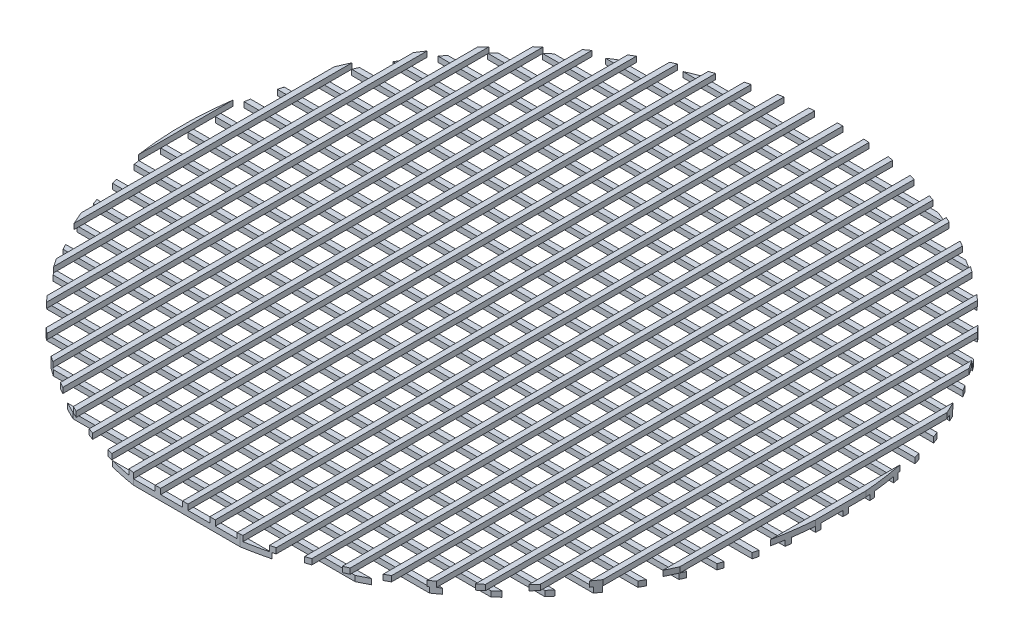
SolidWorks part; units mm, degrees
material "1023 Carbon Steel Sheet (SS)"
ref_plane "Front Plane" through (0, 0, 0) normal (0, 0, 1) x (1, 0, 0)
ref_plane "Top Plane" through (0, 0, 0) normal (0, 1, 0) x (1, 0, 0)
ref_plane "Right Plane" through (0, 0, 0) normal (1, 0, 0) x (0, 0, -1)
sketch "Sketch1" plane through (0, 0, 0) normal (0, 1, 0) x (1, 0, 0)
  line L0 (-34.035, 32.5183) -> (-33.935, 32.5183)
  line L1 (-34.535, 32.5183) -> (-34.435, 32.5183)
  line L2 (-34.535, 32.5183) -> (-34.535, 20.5183)
  line L3 (-34.535, 20.5183) -> (-34.435, 20.5183)
  line L4 (-34.435, 32.5183) -> (-34.435, 20.5183)
  line L5 (-34.035, 32.5183) -> (-34.035, 20.5183)
  line L6 (-34.035, 20.5183) -> (-33.935, 20.5183)
  line L7 (-33.935, 32.5183) -> (-33.935, 20.5183)
  line L8 (-33.535, 32.5183) -> (-33.435, 32.5183)
  line L9 (-33.535, 32.5183) -> (-33.535, 20.5183)
  line L10 (-33.535, 20.5183) -> (-33.435, 20.5183)
  line L11 (-33.435, 32.5183) -> (-33.435, 20.5183)
  line L12 (-33.035, 32.5183) -> (-32.935, 32.5183)
  line L13 (-33.035, 32.5183) -> (-33.035, 20.5183)
  line L14 (-33.035, 20.5183) -> (-32.935, 20.5183)
  line L15 (-32.935, 32.5183) -> (-32.935, 20.5183)
  line L16 (-32.535, 32.5183) -> (-32.435, 32.5183)
  line L17 (-32.535, 32.5183) -> (-32.535, 20.5183)
  line L18 (-32.535, 20.5183) -> (-32.435, 20.5183)
  line L19 (-32.435, 32.5183) -> (-32.435, 20.5183)
  line L20 (-32.035, 32.5183) -> (-31.935, 32.5183)
  line L21 (-32.035, 32.5183) -> (-32.035, 20.5183)
  line L22 (-32.035, 20.5183) -> (-31.935, 20.5183)
  line L23 (-31.935, 32.5183) -> (-31.935, 20.5183)
  line L24 (-31.535, 32.5183) -> (-31.435, 32.5183)
  line L25 (-31.535, 32.5183) -> (-31.535, 20.5183)
  line L26 (-31.535, 20.5183) -> (-31.435, 20.5183)
  line L27 (-31.435, 32.5183) -> (-31.435, 20.5183)
  line L28 (-31.035, 32.5183) -> (-30.935, 32.5183)
  line L29 (-31.035, 32.5183) -> (-31.035, 20.5183)
  line L30 (-31.035, 20.5183) -> (-30.935, 20.5183)
  line L31 (-30.935, 32.5183) -> (-30.935, 20.5183)
  line L32 (-30.535, 32.5183) -> (-30.435, 32.5183)
  line L33 (-30.535, 32.5183) -> (-30.535, 20.5183)
  line L34 (-30.535, 20.5183) -> (-30.435, 20.5183)
  line L35 (-30.435, 32.5183) -> (-30.435, 20.5183)
  line L36 (-30.035, 32.5183) -> (-29.935, 32.5183)
  line L37 (-30.035, 32.5183) -> (-30.035, 20.5183)
  line L38 (-30.035, 20.5183) -> (-29.935, 20.5183)
  line L39 (-29.935, 32.5183) -> (-29.935, 20.5183)
  line L40 (-29.535, 32.5183) -> (-29.435, 32.5183)
  line L41 (-29.535, 32.5183) -> (-29.535, 20.5183)
  line L42 (-29.535, 20.5183) -> (-29.435, 20.5183)
  line L43 (-29.435, 32.5183) -> (-29.435, 20.5183)
  line L44 (-29.035, 32.5183) -> (-28.935, 32.5183)
  line L45 (-29.035, 32.5183) -> (-29.035, 20.5183)
  line L46 (-29.035, 20.5183) -> (-28.935, 20.5183)
  line L47 (-28.935, 32.5183) -> (-28.935, 20.5183)
  line L48 (-28.535, 32.5183) -> (-28.435, 32.5183)
  line L49 (-28.535, 32.5183) -> (-28.535, 20.5183)
  line L50 (-28.535, 20.5183) -> (-28.435, 20.5183)
  line L51 (-28.435, 32.5183) -> (-28.435, 20.5183)
  line L52 (-35.035, 32.5183) -> (-34.935, 32.5183)
  line L53 (-35.035, 32.5183) -> (-35.035, 20.5183)
  line L54 (-35.035, 20.5183) -> (-34.935, 20.5183)
  line L55 (-34.935, 32.5183) -> (-34.935, 20.5183)
  line L56 (-35.535, 32.5183) -> (-35.435, 32.5183)
  line L57 (-35.535, 32.5183) -> (-35.535, 20.5183)
  line L58 (-35.535, 20.5183) -> (-35.435, 20.5183)
  line L59 (-35.435, 32.5183) -> (-35.435, 20.5183)
  line L60 (-36.035, 32.5183) -> (-35.935, 32.5183)
  line L61 (-36.035, 32.5183) -> (-36.035, 20.5183)
  line L62 (-36.035, 20.5183) -> (-35.935, 20.5183)
  line L63 (-35.935, 32.5183) -> (-35.935, 20.5183)
  line L64 (-36.535, 32.5183) -> (-36.435, 32.5183)
  line L65 (-36.535, 32.5183) -> (-36.535, 20.5183)
  line L66 (-36.535, 20.5183) -> (-36.435, 20.5183)
  line L67 (-36.435, 32.5183) -> (-36.435, 20.5183)
  line L68 (-37.035, 32.5183) -> (-36.935, 32.5183)
  line L69 (-37.035, 32.5183) -> (-37.035, 20.5183)
  line L70 (-37.035, 20.5183) -> (-36.935, 20.5183)
  line L71 (-36.935, 32.5183) -> (-36.935, 20.5183)
  line L72 (-37.535, 32.5183) -> (-37.435, 32.5183)
  line L73 (-37.535, 32.5183) -> (-37.535, 20.5183)
  line L74 (-37.535, 20.5183) -> (-37.435, 20.5183)
  line L75 (-37.435, 32.5183) -> (-37.435, 20.5183)
  line L76 (-38.035, 32.5183) -> (-37.935, 32.5183)
  line L77 (-38.035, 32.5183) -> (-38.035, 20.5183)
  line L78 (-38.035, 20.5183) -> (-37.935, 20.5183)
  line L79 (-37.935, 32.5183) -> (-37.935, 20.5183)
  line L80 (-38.535, 32.5183) -> (-38.435, 32.5183)
  line L81 (-38.535, 32.5183) -> (-38.535, 20.5183)
  line L82 (-38.535, 20.5183) -> (-38.435, 20.5183)
  line L83 (-38.435, 32.5183) -> (-38.435, 20.5183)
  line L84 (-39.035, 32.5183) -> (-38.935, 32.5183)
  line L85 (-39.035, 32.5183) -> (-39.035, 20.5183)
  line L86 (-39.035, 20.5183) -> (-38.935, 20.5183)
  line L87 (-38.935, 32.5183) -> (-38.935, 20.5183)
  line L88 (-39.535, 32.5183) -> (-39.435, 32.5183)
  line L89 (-39.535, 32.5183) -> (-39.535, 20.5183)
  line L90 (-39.535, 20.5183) -> (-39.435, 20.5183)
  line L91 (-39.435, 32.5183) -> (-39.435, 20.5183)
  line L92 (-40.035, 32.5183) -> (-39.935, 32.5183)
  line L93 (-40.035, 32.5183) -> (-40.035, 20.5183)
  line L94 (-40.035, 20.5183) -> (-39.935, 20.5183)
  line L95 (-39.935, 32.5183) -> (-39.935, 20.5183)
  line L96 (-40.535, 32.5183) -> (-40.435, 32.5183)
  line L97 (-40.535, 32.5183) -> (-40.535, 20.5183)
  line L98 (-40.535, 20.5183) -> (-40.435, 20.5183)
  line L99 (-40.435, 32.5183) -> (-40.435, 20.5183)
  line L100 (-34.435, 26.5183) -> (-34.535, 26.5183) construction
  point P102 (-34.485, 26.5183)
  dimension "D1" = 0.1
  dimension "D2" = 12
extrude "Boss-Extrude2" add sketch "Sketch1" along normal blind 0.1
sketch "Sketch3" plane through (0, 0, 0) normal (0, 1, 0) x (1, 0, 0)
  line L0 (-28.435, 21.0183) -> (-40.435, 21.0183)
  line L1 (-28.435, 20.5183) -> (-40.435, 20.5183)
  line L2 (-28.435, 20.5183) -> (-28.435, 20.6183)
  line L3 (-28.435, 20.6183) -> (-40.435, 20.6183)
  line L4 (-40.435, 20.5183) -> (-40.435, 20.6183)
  line L5 (-28.435, 21.1183) -> (-40.435, 21.1183)
  line L6 (-28.435, 21.0183) -> (-28.435, 21.1183)
  line L7 (-40.435, 21.0183) -> (-40.435, 21.1183)
  line L8 (-28.435, 21.5183) -> (-40.435, 21.5183)
  line L9 (-28.435, 21.6183) -> (-40.435, 21.6183)
  line L10 (-28.435, 21.5183) -> (-28.435, 21.6183)
  line L11 (-40.435, 21.5183) -> (-40.435, 21.6183)
  line L12 (-28.435, 22.0183) -> (-40.435, 22.0183)
  line L13 (-28.435, 22.1183) -> (-40.435, 22.1183)
  line L14 (-28.435, 22.0183) -> (-28.435, 22.1183)
  line L15 (-40.435, 22.0183) -> (-40.435, 22.1183)
  line L16 (-28.435, 22.5183) -> (-40.435, 22.5183)
  line L17 (-28.435, 22.6183) -> (-40.435, 22.6183)
  line L18 (-28.435, 22.5183) -> (-28.435, 22.6183)
  line L19 (-40.435, 22.5183) -> (-40.435, 22.6183)
  line L20 (-28.435, 23.0183) -> (-40.435, 23.0183)
  line L21 (-28.435, 23.1183) -> (-40.435, 23.1183)
  line L22 (-28.435, 23.0183) -> (-28.435, 23.1183)
  line L23 (-40.435, 23.0183) -> (-40.435, 23.1183)
  line L24 (-28.435, 23.5183) -> (-40.435, 23.5183)
  line L25 (-28.435, 23.6183) -> (-40.435, 23.6183)
  line L26 (-28.435, 23.5183) -> (-28.435, 23.6183)
  line L27 (-40.435, 23.5183) -> (-40.435, 23.6183)
  line L28 (-28.435, 24.0183) -> (-40.435, 24.0183)
  line L29 (-28.435, 24.1183) -> (-40.435, 24.1183)
  line L30 (-28.435, 24.0183) -> (-28.435, 24.1183)
  line L31 (-40.435, 24.0183) -> (-40.435, 24.1183)
  line L32 (-28.435, 24.5183) -> (-40.435, 24.5183)
  line L33 (-28.435, 24.6183) -> (-40.435, 24.6183)
  line L34 (-28.435, 24.5183) -> (-28.435, 24.6183)
  line L35 (-40.435, 24.5183) -> (-40.435, 24.6183)
  line L36 (-28.435, 25.0183) -> (-40.435, 25.0183)
  line L37 (-28.435, 25.1183) -> (-40.435, 25.1183)
  line L38 (-28.435, 25.0183) -> (-28.435, 25.1183)
  line L39 (-40.435, 25.0183) -> (-40.435, 25.1183)
  line L40 (-28.435, 25.5183) -> (-40.435, 25.5183)
  line L41 (-28.435, 25.6183) -> (-40.435, 25.6183)
  line L42 (-28.435, 25.5183) -> (-28.435, 25.6183)
  line L43 (-40.435, 25.5183) -> (-40.435, 25.6183)
  line L44 (-28.435, 26.0183) -> (-40.435, 26.0183)
  line L45 (-28.435, 26.1183) -> (-40.435, 26.1183)
  line L46 (-28.435, 26.0183) -> (-28.435, 26.1183)
  line L47 (-40.435, 26.0183) -> (-40.435, 26.1183)
  line L48 (-28.435, 26.5183) -> (-40.435, 26.5183)
  line L49 (-28.435, 26.6183) -> (-40.435, 26.6183)
  line L50 (-28.435, 26.5183) -> (-28.435, 26.6183)
  line L51 (-40.435, 26.5183) -> (-40.435, 26.6183)
  line L52 (-28.435, 27.0183) -> (-40.435, 27.0183)
  line L53 (-28.435, 27.1183) -> (-40.435, 27.1183)
  line L54 (-28.435, 27.0183) -> (-28.435, 27.1183)
  line L55 (-40.435, 27.0183) -> (-40.435, 27.1183)
  line L56 (-28.435, 27.5183) -> (-40.435, 27.5183)
  line L57 (-28.435, 27.6183) -> (-40.435, 27.6183)
  line L58 (-28.435, 27.5183) -> (-28.435, 27.6183)
  line L59 (-40.435, 27.5183) -> (-40.435, 27.6183)
  line L60 (-28.435, 28.0183) -> (-40.435, 28.0183)
  line L61 (-28.435, 28.1183) -> (-40.435, 28.1183)
  line L62 (-28.435, 28.0183) -> (-28.435, 28.1183)
  line L63 (-40.435, 28.0183) -> (-40.435, 28.1183)
  line L64 (-28.435, 28.5183) -> (-40.435, 28.5183)
  line L65 (-28.435, 28.6183) -> (-40.435, 28.6183)
  line L66 (-28.435, 28.5183) -> (-28.435, 28.6183)
  line L67 (-40.435, 28.5183) -> (-40.435, 28.6183)
  line L68 (-28.435, 29.0183) -> (-40.435, 29.0183)
  line L69 (-28.435, 29.1183) -> (-40.435, 29.1183)
  line L70 (-28.435, 29.0183) -> (-28.435, 29.1183)
  line L71 (-40.435, 29.0183) -> (-40.435, 29.1183)
  line L72 (-28.435, 29.5183) -> (-40.435, 29.5183)
  line L73 (-28.435, 29.6183) -> (-40.435, 29.6183)
  line L74 (-28.435, 29.5183) -> (-28.435, 29.6183)
  line L75 (-40.435, 29.5183) -> (-40.435, 29.6183)
  line L76 (-28.435, 30.0183) -> (-40.435, 30.0183)
  line L77 (-28.435, 30.1183) -> (-40.435, 30.1183)
  line L78 (-28.435, 30.0183) -> (-28.435, 30.1183)
  line L79 (-40.435, 30.0183) -> (-40.435, 30.1183)
  line L80 (-28.435, 30.5183) -> (-40.435, 30.5183)
  line L81 (-28.435, 30.6183) -> (-40.435, 30.6183)
  line L82 (-28.435, 30.5183) -> (-28.435, 30.6183)
  line L83 (-40.435, 30.5183) -> (-40.435, 30.6183)
  line L84 (-28.435, 31.0183) -> (-40.435, 31.0183)
  line L85 (-28.435, 31.1183) -> (-40.435, 31.1183)
  line L86 (-28.435, 31.0183) -> (-28.435, 31.1183)
  line L87 (-40.435, 31.0183) -> (-40.435, 31.1183)
  line L88 (-28.435, 31.5183) -> (-40.435, 31.5183)
  line L89 (-28.435, 31.6183) -> (-40.435, 31.6183)
  line L90 (-28.435, 31.5183) -> (-28.435, 31.6183)
  line L91 (-40.435, 31.5183) -> (-40.435, 31.6183)
  line L92 (-28.435, 32.0183) -> (-40.435, 32.0183)
  line L93 (-28.435, 32.1183) -> (-40.435, 32.1183)
  line L94 (-28.435, 32.0183) -> (-28.435, 32.1183)
  line L95 (-40.435, 32.0183) -> (-40.435, 32.1183)
  line L96 (-28.435, 32.5183) -> (-40.435, 32.5183)
  line L97 (-28.435, 32.6183) -> (-40.435, 32.6183)
  line L98 (-28.435, 32.5183) -> (-28.435, 32.6183)
  line L99 (-40.435, 32.5183) -> (-40.435, 32.6183)
  dimension "D1" = 0.1
  dimension "D2" = 12
  dimension "D3" = 25
extrude "Boss-Extrude5" add sketch "Sketch3" against normal blind 0.1
sketch "Sketch4" plane through (0, 0, 0) normal (0, 1, 0) x (1, 0, 0)
  circle A0 centre (-34.4572, 26.4785) radius 6.0398
extrude "Cut-Extrude2" cut sketch "Sketch4" against normal through all flip side to cut
extrude "Cut-Extrude4" cut sketch "Sketch4<2>" along normal through all flip side to cut
sketch "Sketch4<2>" plane through (0, 0, 0) normal (0, 1, 0) x (1, 0, 0) same geometry as "Sketch4"
